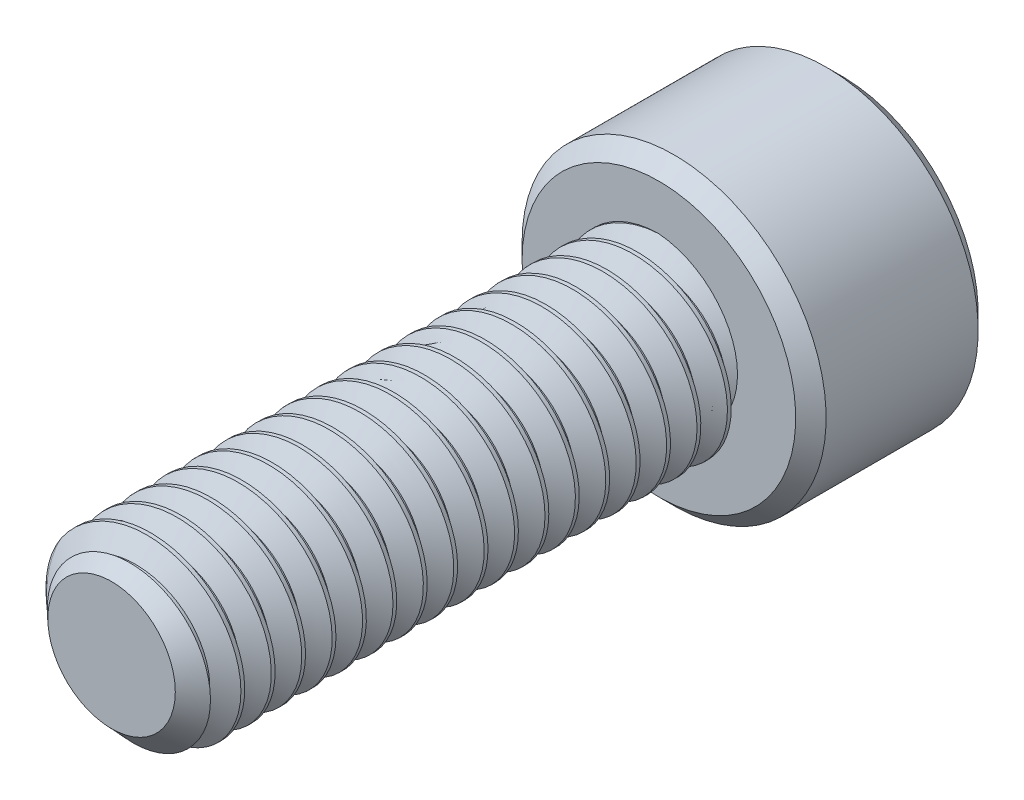
SolidWorks part; units mm, degrees
material "AISI 304"
ref_plane "Front Plane" through (0, 0, 0) normal (0, 0, 1) x (1, 0, 0)
ref_plane "Top Plane" through (0, 0, 0) normal (0, 1, 0) x (1, 0, 0)
ref_plane "Right Plane" through (0, 0, 0) normal (1, 0, 0) x (0, 0, -1)
sketch "Sketch1" plane through (0, 0, 0) normal (0, 0, 1) x (1, 0, 0)
  circle A0 centre (0, 0) radius 3
  dimension "OD" = 6
extrude "Extrude1" add sketch "Sketch1" against normal blind 18
sketch "Sketch2" plane through (0, 0, 0) normal (0, 0, 1) x (1, 0, 0)
  circle A0 centre (0, 0) radius 3 construction
  circle A1 centre (0, 0) radius 3
curve "Helix/Spiral1" pitch 1 height 19 turns 19 parameters "pitch"=1
sketch "Sketch3" plane through (0, 0, 0) normal (1, 0, 0) x (0, 0, -1)
  line L0 (-0.875, 3) -> (-0.5, 2.3505)
  line L1 (-0.5, 2.3505) -> (-0.375, 2.3505)
  line L2 (-0.375, 2.3505) -> (0, 3)
  line L3 (-0.875, 3) -> (0, 3)
  line L4 (-0.4375, 3) -> (-0.4375, 2.3505) construction
  line L5 (-0.6875, 2.6752) -> (-0.1875, 2.6752) construction
  line L6 (0, 3) -> (0, -3) construction
  dimension "D1" = 0.125
  dimension "D2" = 0.5
  dimension "D3" = 60
sweep "Cut-Sweep1" cut profiles "Sketch3" path "Helix/Spiral1"
sketch "Sketch4" plane through (0, 0, 0) normal (1, 0, 0) x (0, 0, -1)
  line L0 (0.8425, 3) -> (0, 2.0965)
  line L1 (0, 2.0965) -> (0, 3)
  line L2 (0.8425, 3) -> (0, 3)
  line L3 (-0.875, 3) -> (0, 3) construction
  line L4 (0, 0) -> (7.0209, 0) construction
  dimension "D1" = 47
  dimension "D2" = 0.254
revolve "Cut-Revolve1" cut sketch "Sketch4" angle 360 about L4
sketch "Sketch5" plane through (0, 0, 0) normal (1, 0, 0) x (0, 0, -1)
  line L0 (18, -2.3644) -> (18, 2.1406) construction
  line L1 (18, 3.127) -> (28.1202, 3.127)
  line L2 (18, 3.127) -> (18, 0)
  line L3 (18, 0) -> (28, 0)
  line L4 (28, 2.7968) -> (28, 0)
  line L5 (28.1202, 3.127) -> (28, 2.7968)
  line L6 (0, 0) -> (9.9695, 0) construction
  point P3 (28, 3.127)
  point P10 (28, 3.127)
  dimension "D1" = 0.3302
  dimension "Thread min" = 28
  dimension "D2" = 0.127
  dimension "D3" = 20
revolve "partially thread" [suppressed] add sketch "Sketch5" angle 360 about L6
sketch "Sketch6" plane through (0, 0, -18) normal (0, 0, -1) x (-1, 0, 0)
  circle A0 centre (0, 0) radius 5
  dimension "head dia" = 10
extrude "Extrude2" add sketch "Sketch6" along normal blind 6
sketch "Sketch7" plane through (0, 0, -24) normal (0, 0, -1) x (-1, 0, 0)
  line L1 (0, 2.8868) -> (-2.5, 1.4434)
  line L2 (-2.5, 1.4434) -> (-2.5, -1.4434)
  line L3 (-2.5, -1.4434) -> (0, -2.8868)
  line L4 (0, -2.8868) -> (2.5, -1.4434)
  line L5 (2.5, -1.4434) -> (2.5, 1.4434)
  line L6 (2.5, 1.4434) -> (0, 2.8868)
  circle A0 centre (0, 0) radius 2.5 construction
  dimension "hex dia" = 5
extrude "Cut-Extrude1" cut sketch "Sketch7" against normal blind 3.75
sketch "Sketch8" plane through (0, 0, -24) normal (0, 0, -1) x (-1, 0, 0)
  circle A0 centre (0, 0) radius 2.8868
extrude "Cut-Extrude2" cut sketch "Sketch8" against normal through all draft 45
chamfer "Chamfer1" distance 0.5 angle 45 2 edges at (-5, 0, -24) (-5, 0, -18)
sketch "Sketch9" plane through (0, 0, 0) normal (1, 0, 0) x (0, 0, -1)
  line L0 (0, 3) -> (0, -3) construction
  line L1 (5.5, 3) -> (5.5, -3) construction
  dimension "D1" = 5.5
  dimension "D4" = 0.635
  dimension "D5" = 0.3302
equation "\"D3@Helix/Spiral1\" = \"screw length@Extrude1\"+\"pitch@Helix/Spiral1\""
equation "\"D1@Sketch3\" = \"pitch@Helix/Spiral1\"*.125"
equation "\"D2@Sketch3\" = \"pitch@Helix/Spiral1\"*.5"
equation "\"D1@Cut-Extrude1\" = \"hex dia@Sketch7\"*.75"
equation "\"D1@Chamfer1\" = \"head dia@Sketch6\"*.05"
equation "\"D1@Sketch9\" = \"pitch@Helix/Spiral1\"*5.5"
